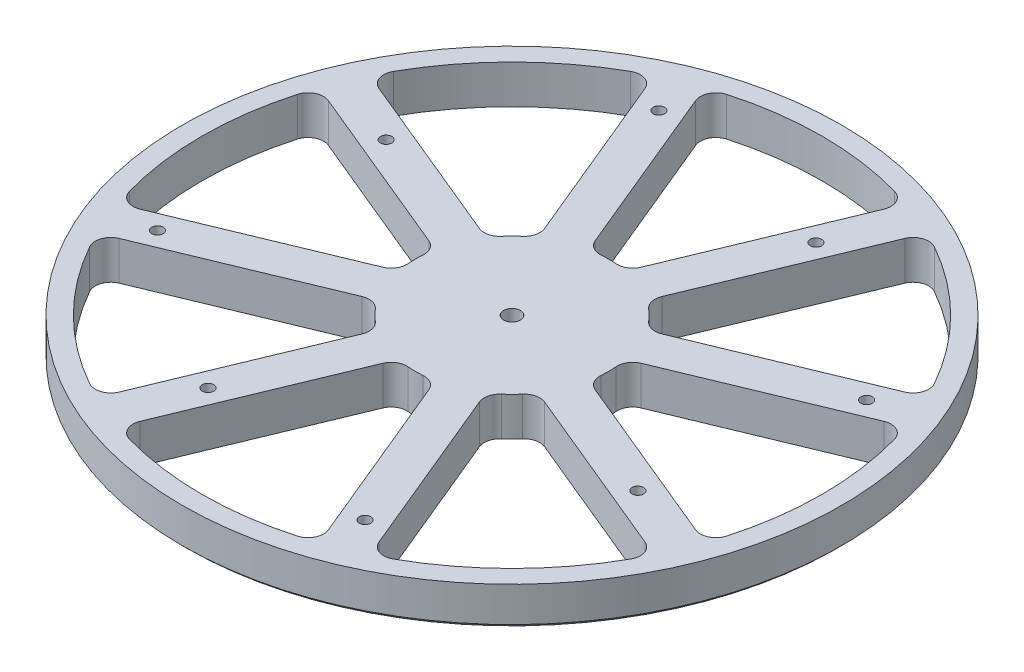
SolidWorks part; units mm, degrees
ref_plane "Front Plane" through (0, 0, 0) normal (0, 0, 1) x (1, 0, 0)
ref_plane "Top Plane" through (0, 0, 0) normal (0, 1, 0) x (1, 0, 0)
ref_plane "Right Plane" through (0, 0, 0) normal (1, 0, 0) x (0, 0, -1)
sketch "Sketch2" plane through (0, 0, 0) normal (1, 0, 0) x (0, 0, -1)
  line L0 (0, 0) -> (-84.9998, 0)
  line L1 (-84.9998, 0) -> (-84.9998, 10)
  line L2 (-84.9998, 10) -> (0, 10)
  line L5 (0, 10) -> (0, 0)
  dimension "D1" = 84.9998
  dimension "D2" = 10
ref_axis "Axis1" through (0, -0.75, 0) along (0, 1, 0)
revolve "Revolve1" add sketch "Sketch2" angle 360 about axis through (0, -0.75, 0) along (0, 1, 0)
hole_wizard "#32 (0.116) Diameter Hole1" positions "Sketch6" profile "Sketch7" hole size "#32" standard "ANSI Inch" end condition through all
sketch "Sketch6" plane through (0, 10, 0) normal (0, 1, 0) x (1, 0, 0)
  line L0 (0, 0) -> (-53.438, 129.0108) construction
  line L2 (0, 0) -> (0, 109.0908) construction
  line L3 (0, 0) -> (-78.5296, 32.528) construction
  circle A0 centre (0, 0) radius 84.9998 construction
  point P0 (-26.7878, 64.6716)
  point P18 (-55.4328, 22.961)
  dimension "D1" = 22.5
  dimension "D2" = 70
  dimension "D3" = 45
  dimension "D4" = 60
sketch "Sketch7" plane through (-26.7878, 10, -64.6716) normal (1, 0, 0) x (0, 0, 1)
  line L0 (0, 0) -> (0, 10)
  line L1 (0, 10) -> (1.4732, 10)
  line L2 (1.4732, 10) -> (1.4732, 0)
  line L5 (1.4732, 0) -> (0, 0)
  line L11 (0, -6.35) -> (0, 107.95) construction
  dimension "Thru Hole Dia." = 2.9464
  dimension "Thru Hole Depth" = 10
pattern_circular "CirPattern3" count 4 over 360 about axis through (0, -0.75, 0) along (0, 1, 0) of "#32 (0.116) Diameter Hole1"
sketch "Sketch8" plane through (0, 10, 0) normal (0, 1, 0) x (1, 0, 0)
  line L4 (0, 0) -> (0, 93.9995) construction
  line L5 (0, 0) -> (113.8372, 0) construction
  line L6 (-4.7544, 24.5438) -> (-25.9354, 75.6791)
  line L7 (4.7544, 24.5438) -> (25.9354, 75.6791)
  line L8 (0, 0) -> (-26.7878, 64.6716) construction
  arc A0 (-4.7544, 24.5438) -> (4.7544, 24.5438) centre (0, 0) cw
  arc A1 (-25.9354, 75.6791) -> (25.9354, 75.6791) centre (0, 0) cw
  circle A2 centre (0, 0) radius 84.9998 construction
  dimension "D1" = 25
  dimension "D2" = 5
  dimension "D3" = 5
extrude "Cut-Extrude1" cut sketch "Sketch8" against normal through all
fillet "Fillet1" radius 4 4 edges at (4.7544, 5, -24.5438) (25.9354, 5, -75.6791) (-4.7544, 5, -24.5438) (-25.9354, 5, -75.6791)
pattern_circular "CirPattern4" count 8 over 360 about axis through (0, -0.75, 0) along (0, 1, 0) of "Cut-Extrude1", "Fillet1"
chamfer "Chamfer2" distance 1 angle 45 1 edges at (0, 0, -84.9998)
hole_wizard "#18 (0.1695) Diameter Hole1" positions "Sketch9" profile "Sketch11" hole size "#18" standard "ANSI Inch" end condition through all
sketch "Sketch9" plane through (0, 0, 0) normal (0, -1, 0) x (-1, 0, 0)
  point P0 (0, 0)
sketch "Sketch11" plane through (0, 0, 0) normal (1, 0, 0) x (0, 0, -1)
  line L0 (0, 0) -> (0, 10)
  line L1 (0, 10) -> (2.1526, 10)
  line L2 (2.1526, 10) -> (2.1526, 0)
  line L5 (2.1526, 0) -> (0, 0)
  line L11 (0, -6.35) -> (0, 107.95) construction
  dimension "Thru Hole Dia." = 4.3053
  dimension "Thru Hole Depth" = 10
